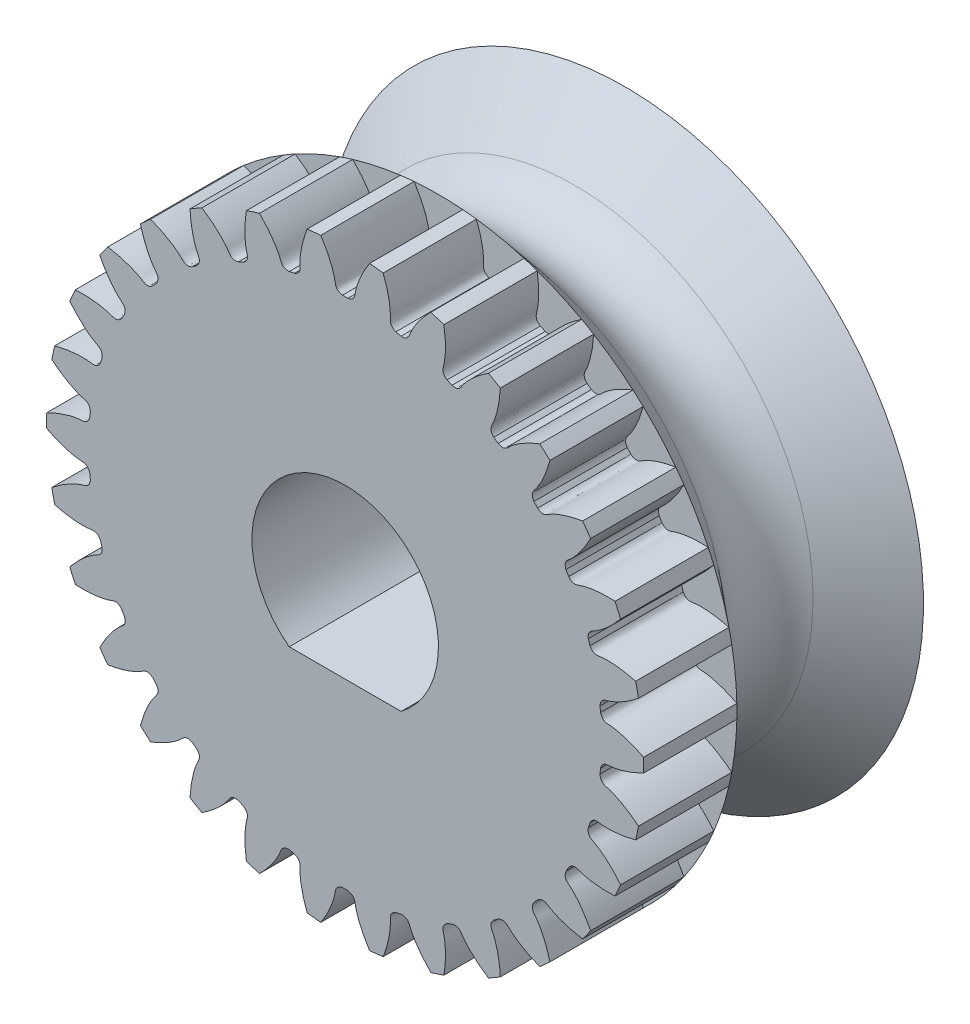
SolidWorks part; units mm, degrees
ref_plane "前视基准面" through (0, 0, 0) normal (0, 0, 1) x (1, 0, 0)
ref_plane "上视基准面" through (0, 0, 0) normal (0, 1, 0) x (1, 0, 0)
ref_plane "右视基准面" through (0, 0, 0) normal (1, 0, 0) x (0, 0, -1)
sketch "草图1" plane through (0, 0, 0) normal (0, 0, 1) x (1, 0, 0)
  circle A0 centre (0, 0) radius 16
extrude "凸台-拉伸1" add sketch "草图1" along normal blind 5
ref_axis "基准轴1" through (0, 0, -1.5) along (0, 0, 1)
sketch "草图2" plane through (0, 0, 0) normal (0, 0, 1) x (1, 0, 0)
  line L0 (0, 0) -> (0, 16) construction
  circle A0 centre (0, 0) radius 16 construction
  arc A1 (0.1456, 13.7492) -> (-0.1456, 13.7492) centre (0, 0) ccw
  arc A2 (3.3663, 18.1906) -> (-3.3663, 18.1906) centre (0, 0) ccw
  spline S0 degree 3 poles (0.1456, 13.7492) (0.5082, 13.813) (0.5103, 14.0471) (0.559, 14.2886) (0.57, 14.3381) (0.5832, 14.3929) (0.5991, 14.4529) (0.6176, 14.518) (0.6391, 14.588) (0.6638, 14.663) (0.6918, 14.7428) (0.7234, 14.8273) (0.7588, 14.9164) (0.7981, 15.01) (0.8416, 15.1079) (0.8894, 15.21) (0.9417, 15.3163) (0.9987, 15.4264) (1.0606, 15.5404) (1.1276, 15.658) (1.1998, 15.779) (1.2774, 15.9034) (1.3605, 16.031) (1.4494, 16.1615) (1.5441, 16.2948) (1.6448, 16.4307) (1.7516, 16.569) (1.8647, 16.7096) (1.9843, 16.8522) (2.1103, 16.9966) (2.2431, 17.1427) (2.3825, 17.2901) (2.5289, 17.4388) (2.6823, 17.5884) (2.8427, 17.7389) (3.0689, 17.9426) (3.2453, 18.0921) (3.3663, 18.1906) knots 0 0 0 0 0.115324 0.123413 0.132512 0.142623 0.153745 0.165878 0.179022 0.193177 0.208343 0.22452 0.241708 0.259907 0.279117 0.299338 0.320571 0.342814 0.366068 0.390334 0.41561 0.441898 0.469196 0.497506 0.526827 0.557158 0.588501 0.620855 0.65422 0.688595 0.723982 0.76038 0.797789 0.836209 0.87564 0.916083 1 1 1 1
  spline S1 degree 3 poles (-0.1456, 13.7492) (-0.5082, 13.813) (-0.5103, 14.0471) (-0.559, 14.2886) (-0.57, 14.3381) (-0.5832, 14.3929) (-0.5991, 14.4529) (-0.6176, 14.518) (-0.6391, 14.588) (-0.6638, 14.663) (-0.6918, 14.7428) (-0.7234, 14.8273) (-0.7588, 14.9164) (-0.7981, 15.01) (-0.8416, 15.1079) (-0.8894, 15.21) (-0.9417, 15.3163) (-0.9987, 15.4264) (-1.0606, 15.5404) (-1.1276, 15.658) (-1.1998, 15.779) (-1.2774, 15.9034) (-1.3605, 16.031) (-1.4494, 16.1615) (-1.5441, 16.2948) (-1.6448, 16.4307) (-1.7516, 16.569) (-1.8647, 16.7096) (-1.9843, 16.8522) (-2.1103, 16.9966) (-2.2431, 17.1427) (-2.3825, 17.2901) (-2.5289, 17.4388) (-2.6823, 17.5884) (-2.8427, 17.7389) (-3.0689, 17.9426) (-3.2453, 18.0921) (-3.3663, 18.1906) knots 0 0 0 0 0.115324 0.123413 0.132512 0.142623 0.153745 0.165878 0.179022 0.193177 0.208343 0.22452 0.241708 0.259907 0.279117 0.299338 0.320571 0.342814 0.366068 0.390334 0.41561 0.441898 0.469196 0.497506 0.526827 0.557158 0.588501 0.620855 0.65422 0.688595 0.723982 0.76038 0.797789 0.836209 0.87564 0.916083 1 1 1 1
extrude "切除-拉伸1" cut sketch "草图2" along normal through all
pattern_circular "阵列(圆周)1" count 30 every 12 about axis through (0, 0, -1.5) along (0, 0, 1) of "切除-拉伸1"
sketch "草图3" plane through (0, 0, 0) normal (0, 0, 1) x (1, 0, 0)
  circle A0 centre (0, 0) radius 15 construction
  dimension "Dn" = 30
sketch "草图4" plane through (0, 0, 0) normal (0, 1, 0) x (1, 0, 0)
  line L0 (0, 8.6308) -> (0, -7.3249) construction
  line L1 (0, 5) -> (16.342, 5) construction
  line L2 (0, 0) -> (16, 0)
  line L3 (10.4296, 0) -> (8.1994, 0) construction
  line L4 (16, 0) -> (10.0412, 5)
  line L5 (16, 10) -> (10.0412, 5)
  line L6 (0, 10) -> (16, 10)
  line L7 (0, 10) -> (0, 0)
  dimension "D1" = 10
  dimension "D2" = 16
  dimension "D3" = 40
revolve "旋转1" add sketch "草图4" angle 360 about L0
fillet "圆角1" radius 3 1 edges at (-10.0412, 0, -5)
sketch "草图5" plane through (0, 0, -10) normal (0, 0, -1) x (-1, 0, 0)
  line L0 (0, 9.8222) -> (0, -9.1908) construction
  line L1 (-3, -4) -> (3, -4)
  arc A0 (3, -4) -> (-3, -4) centre (0, 0) ccw
  dimension "D1" = 10
  dimension "D2" = 4
extrude "切除-拉伸2" cut sketch "草图5" against normal through all
ref_plane "基准面1" through (0, -20, 0) normal (0, 1, 0) x (1, 0, 0)
sketch "草图6" plane through (0, -20, 0) normal (0, 1, 0) x (1, 0, 0)
  line L0 (0, 0) -> (0, 10) construction
  line L1 (16, 10) -> (-16, 10) construction
  circle A0 centre (0, 5) radius 3
  dimension "D1" = 6
extrude "切除-拉伸3" cut sketch "草图6" along normal blind 12
sketch "草图7" plane through (0, -8, 0) normal (0, -1, 0) x (1, 0, 0)
  circle A0 centre (0, -5) radius 1.6
  dimension "D1" = 3.2
extrude "切除-拉伸4" cut sketch "草图7" against normal up to next and the other way through all
